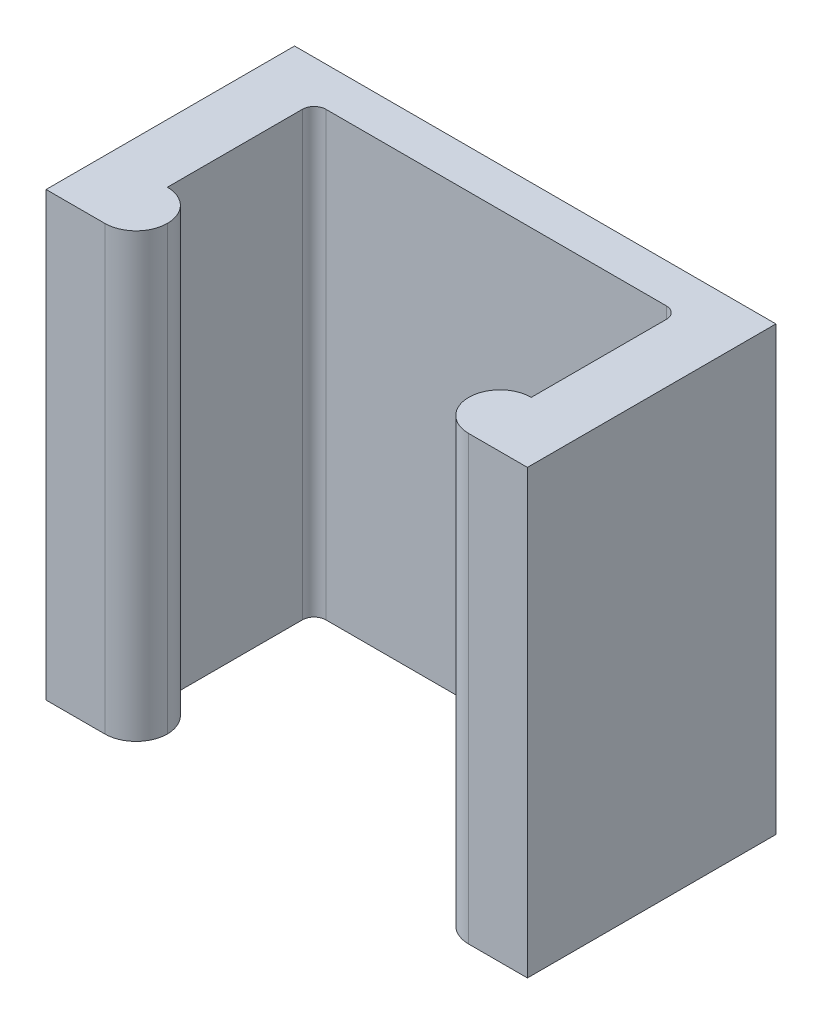
SolidWorks part; units mm, degrees
ref_plane "정면" through (0, 0, 0) normal (0, 0, 1) x (1, 0, 0)
ref_plane "윗면" through (0, 0, 0) normal (0, 1, 0) x (1, 0, 0)
ref_plane "우측면" through (0, 0, 0) normal (1, 0, 0) x (0, 0, -1)
sketch "스케치1" plane through (0, 0, 0) normal (0, 0, 1) x (1, 0, 0)
  line L1 (-6.15, -5.65) -> (6.15, -5.65)
  line L2 (-6.15, -5.65) -> (-6.15, 5.65)
  line L3 (-6.15, 5.65) -> (6.15, 5.65)
  line L4 (6.15, -5.65) -> (6.15, 5.65)
  line L5 (-6.15, -5.65) -> (6.15, 5.65) construction
  line L6 (-6.15, 5.65) -> (6.15, -5.65) construction
  point P0 (0, 0)
  dimension "D1" = 12.3
  dimension "D2" = 11.3
extrude "보스-돌출1" add sketch "스케치1" along normal blind 2
sketch "스케치2" plane through (0, 0, 2) normal (0, 0, 1) x (1, 0, 0)
  line L0 (-6.15, -5.65) -> (6.15, -5.65) construction
  line L1 (-6.15, 5.65) -> (-4.65, 5.65)
  line L2 (-6.15, 5.65) -> (-6.15, -5.65)
  line L3 (-6.15, -5.65) -> (-4.65, -5.65)
  line L4 (-4.65, 5.65) -> (-4.65, -5.65)
  line L6 (6.15, 5.65) -> (4.65, 5.65)
  line L7 (6.15, 5.65) -> (6.15, -5.65)
  line L8 (6.15, -5.65) -> (4.65, -5.65)
  line L9 (4.65, 5.65) -> (4.65, -5.65)
  dimension "D1" = 1.5
  dimension "D2" = 1.5
extrude "보스-돌출2" add sketch "스케치2" along normal blind 4.35
sketch "스케치5" plane through (0, 0, 2) normal (0, 0, 1) x (1, 0, 0)
  line L0 (4.65, 5.65) -> (4.65, -5.65) construction
  line L1 (-4.65, -5.75) -> (4.65, -5.75)
  line L2 (-4.65, -5.75) -> (-4.65, 5.75)
  line L3 (-4.65, 5.75) -> (4.65, 5.75)
  line L4 (4.65, -5.75) -> (4.65, 5.75)
  line L5 (-4.65, -5.75) -> (4.65, 5.75) construction
  line L6 (-4.65, 5.75) -> (4.65, -5.75) construction
  point P0 (0, 0)
  dimension "D1" = 11.5
extrude "컷-돌출1" cut sketch "스케치5" against normal blind 1
sketch "스케치8" plane through (-4.65, 0, 0) normal (1, 0, 0) x (0, 0, -1)
  line L0 (-6.35, -5.65) -> (-1, -5.65) construction
  line L1 (-6.35, 5.65) -> (-4.75, 5.65)
  line L2 (-6.35, 5.65) -> (-6.35, -5.65)
  line L3 (-6.35, -5.65) -> (-4.75, -5.65)
  line L4 (-4.75, 5.65) -> (-4.75, -5.65)
  dimension "D1" = 1.6
extrude "보스-돌출5" add sketch "스케치8" along normal blind 0.8
sketch "스케치9" plane through (4.65, 0, 0) normal (-1, 0, 0) x (0, 0, 1)
  line L0 (6.35, 5.65) -> (1, 5.65) construction
  line L1 (6.35, -5.65) -> (4.75, -5.65)
  line L2 (6.35, -5.65) -> (6.35, 5.65)
  line L3 (6.35, 5.65) -> (4.75, 5.65)
  line L4 (4.75, -5.65) -> (4.75, 5.65)
  dimension "D1" = 1.6
extrude "보스-돌출6" add sketch "스케치9" along normal blind 0.8
fillet "필렛7" radius 0.8 4 edges at (3.85, 0, 6.35) (-3.85, 0, 6.35) (3.85, 0, 4.75) (-3.85, 0, 4.75)
fillet "필렛8" radius 0.3 2 edges at (4.65, 0, 1) (-4.65, 0, 1)
